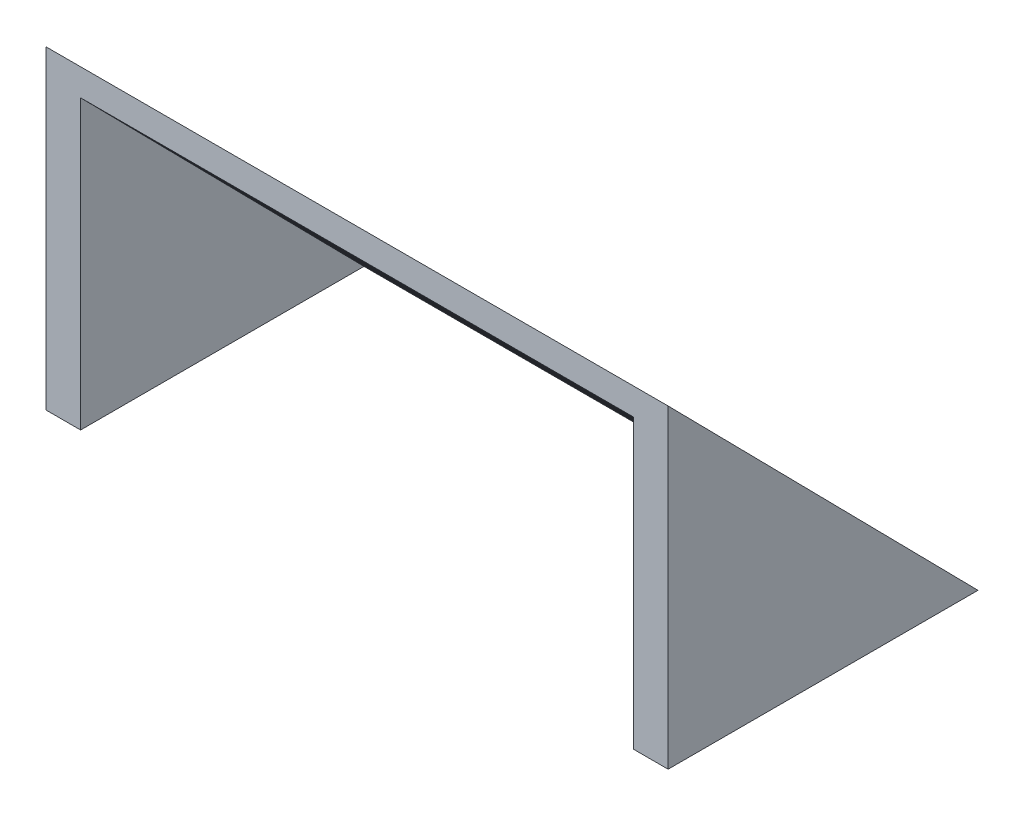
SolidWorks part; units mm, degrees
ref_plane "Přední rovina" through (0, 0, 0) normal (0, 0, 1) x (1, 0, 0)
ref_plane "Horní rovina" through (0, 0, 0) normal (0, 1, 0) x (1, 0, 0)
ref_plane "Pravá rovina" through (0, 0, 0) normal (1, 0, 0) x (0, 0, -1)
sketch "Skica1" plane through (0, 0, 0) normal (1, 0, 0) x (0, 0, -1)
  line L0 (0, 0) -> (0, 20)
  line L1 (0, 20) -> (19.7, 0)
  line L2 (19.7, 0) -> (0, 0)
  dimension "D1" = 19.7
  dimension "20" = 20
extrude "Přidat vysunutím1" add sketch "Skica1" along normal blind 2.2
sketch "Skica2" plane through (0, 9.8489, -9.9989) normal (0, 0.7017, -0.7124) x (-1, 0, 0)
  line L1 (-2.2, 14.2486) -> (-37.35, 14.2486)
  line L2 (-2.2, 14.2486) -> (-2.2, -13.8243)
  line L3 (-2.2, -13.8243) -> (-37.35, -13.8243)
  line L4 (-37.35, 14.2486) -> (-37.35, -13.8243)
  dimension "D1" = 35.15
extrude "Přidat vysunutím2" add sketch "Skica2" against normal blind 1.2
pattern_linear "LinPole1" count 2 spacing 37.35 along (1, 0, 0) of "Přidat vysunutím1"
sketch "Skica3" plane through (39.55, 0, 0) normal (1, 0, 0) x (0, 0, -1)
  line L0 (0, 20) -> (0, 0) construction
  line L1 (0, 16.835) -> (-2.4685, 16.835)
  line L2 (0, 16.835) -> (0, 21.1727)
  line L3 (0, 21.1727) -> (-2.4685, 21.1727)
  line L4 (-2.4685, 16.835) -> (-2.4685, 21.1727)
  line L5 (0, 0) -> (19.7, 0) construction
  line L6 (16.8501, 0) -> (22.214, 0)
  line L7 (16.8501, 0) -> (16.8501, -3.3952)
  line L8 (16.8501, -3.3952) -> (22.214, -3.3952)
  line L9 (22.214, 0) -> (22.214, -3.3952)
extrude "Odebrat vysunutím1" cut sketch "Skica3" against normal through all
